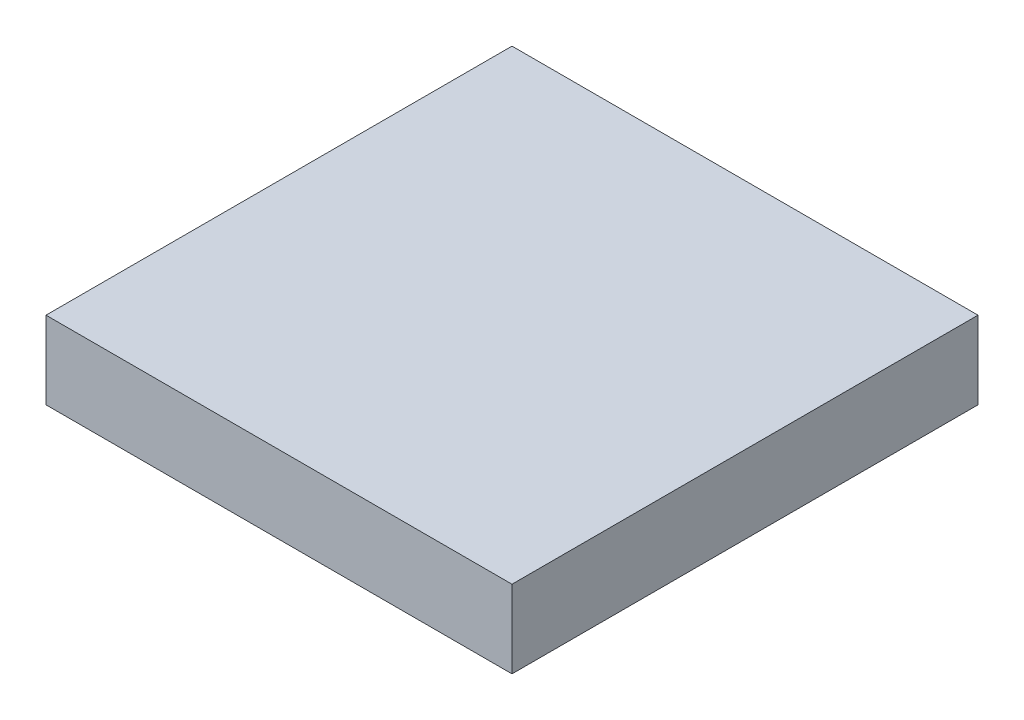
SolidWorks part; units mm, degrees
ref_plane "Front Plane" through (0, 0, 0) normal (0, 0, 1) x (1, 0, 0)
ref_plane "Top Plane" through (0, 0, 0) normal (0, 1, 0) x (1, 0, 0)
ref_plane "Right Plane" through (0, 0, 0) normal (1, 0, 0) x (0, 0, -1)
sketch "Sketch1" plane through (0, 0, 0) normal (0, 1, 0) x (1, 0, 0)
  line L1 (0, 0) -> (300, 0)
  line L2 (0, 0) -> (0, 300)
  line L3 (0, 300) -> (300, 300)
  line L4 (300, 0) -> (300, 300)
  dimension "D1" = 300
  dimension "D2" = 300
extrude "Boss-Extrude1" add sketch "Sketch1" along normal blind 50
